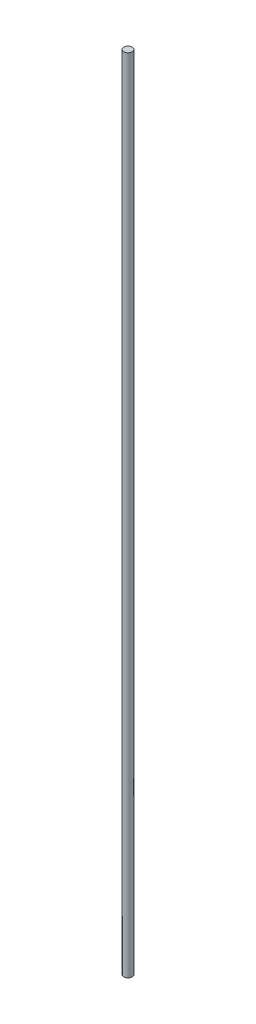
SolidWorks part; units mm, degrees
ref_plane "Front Plane" through (0, 0, 0) normal (0, 0, 1) x (1, 0, 0)
ref_plane "Top Plane" through (0, 0, 0) normal (0, 1, 0) x (1, 0, 0)
ref_plane "Right Plane" through (0, 0, 0) normal (1, 0, 0) x (0, 0, -1)
sketch "Sketch1" plane through (0, 0, 0) normal (0, 1, 0) x (1, 0, 0)
  circle A0 centre (0, 0) radius 3.175
extrude "Boss-Extrude1" add sketch "Sketch1" along normal blind 609.6
